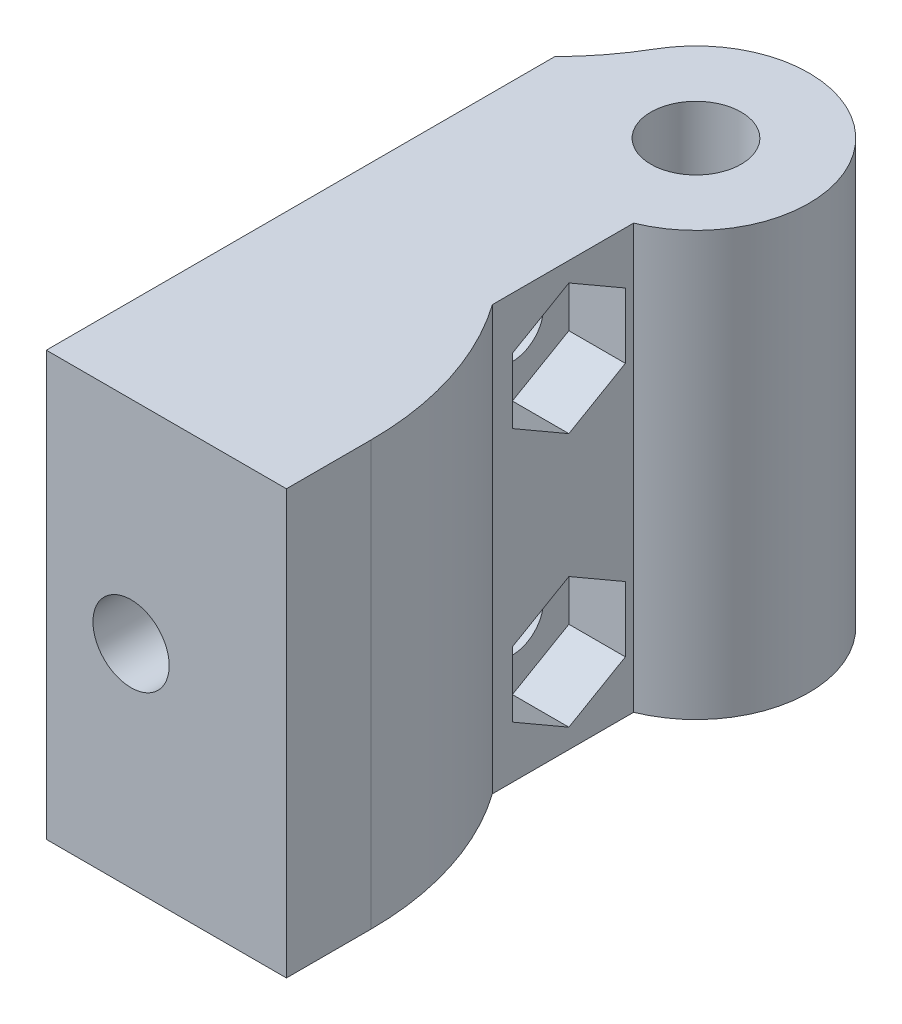
SolidWorks part; units mm, degrees
material "PLA"
ref_plane "前视基准面" through (0, 0, 0) normal (0, 0, 1) x (1, 0, 0)
ref_plane "上视基准面" through (0, 0, 0) normal (0, 1, 0) x (1, 0, 0)
ref_plane "右视基准面" through (0, 0, 0) normal (1, 0, 0) x (0, 0, -1)
sketch "草图1" plane through (0, 0, 0) normal (0, 1, 0) x (1, 0, 0)
  line L2 (-5, -18) -> (3.5, -18)
  line L3 (3.5, -18) -> (3.5, -15)
  line L5 (1.5, -3.7081) -> (1.5, -8.7081)
  line L7 (-5, -18) -> (-5, 0)
  line L8 (-4, 0) -> (-5, 0)
  circle A0 centre (0, 0) radius 1.6
  arc A1 (1.5, -3.7081) -> (-4, 0) centre (0, 0) ccw
  arc A2 (3.5, -15) -> (1.5, -8.7081) centre (-7.397, -15) ccw
  dimension "D1" = 3.2
  dimension "D2" = 4
  dimension "D3" = 18
  dimension "D4" = 8.5
  dimension "D5" = 3
  dimension "D6" = 5
  dimension "D7" = 5
  dimension "D8" = 6.5
extrude "凸台-拉伸1" add sketch "草图1" along normal mid plane 15
sketch "草图3" plane through (1.5, 0, 0) normal (1, 0, 0) x (0, 0, -1)
  line L0 (0, 0) -> (-18, 0) construction
  line L1 (-3.7081, 7.5) -> (-3.7081, -7.5) construction
  line L2 (-6, -7.5) -> (-6, 7.5) construction
  line L3 (-18, 7.5) -> (-18, -7.5) construction
  line L4 (-8.7081, 7.5) -> (-3.7081, 7.5) construction
  circle A0 centre (-6, 4.5) radius 1.1
  circle A1 centre (-6, -4.5) radius 1.1
  circle A2 centre (-6, 4.5) radius 2.2919 construction
  dimension "D1" = 2.2
  dimension "D4" = 4.5838
  dimension "D2" = 9
  dimension "D3" = 6
extrude "切除-拉伸1" cut sketch "草图3" against normal through all both and the other way through all
fillet "圆角1" radius 10 1 edges at (-4, 0, 0)
sketch "草图6" plane through (0, 0, 18) normal (0, 0, 1) x (1, 0, 0)
  line L0 (-2, 0) -> (0, 0) construction
  line L1 (-5, 7.5) -> (-5, -7.5) construction
  circle A0 centre (-2, 0) radius 1.35
  dimension "D2" = 2.7
  dimension "D1" = 3
extrude "切除-拉伸2" cut sketch "草图6" against normal blind 4
sketch "草图7" plane through (-5, 0, 0) normal (-1, 0, 0) x (0, 0, 1)
  line L0 (0, 0) -> (13, 0) construction
  line L1 (0, 7.5) -> (0, -7.5) construction
  line L2 (18, 7.5) -> (18, -7.5) construction
  line L3 (15, -2.5) -> (11, -2.5)
  line L4 (15, -2.5) -> (15, 2.5)
  line L5 (15, 2.5) -> (11, 2.5)
  line L6 (11, -2.5) -> (11, 2.5)
  line L7 (13, 2.5) -> (13, -2.5) construction
  line L8 (15, 0) -> (11, 0) construction
  dimension "D1" = 3
  dimension "D2" = 4
  dimension "D3" = 5
extrude "切除-拉伸3" cut sketch "草图7" against normal blind 6
sketch "草图8" plane through (1.5, 0, 0) normal (1, 0, 0) x (0, 0, -1)
  line L0 (0, 0) -> (-8.7081, 0) construction
  line L1 (-8, 5.6547) -> (-8, 3.3453)
  line L2 (-8, 3.3453) -> (-6, 2.1906)
  line L3 (-6, 2.1906) -> (-4, 3.3453)
  line L4 (-4, 3.3453) -> (-4, 5.6547)
  line L5 (-4, 5.6547) -> (-6, 6.8094)
  line L6 (-6, 6.8094) -> (-8, 5.6547)
  line L7 (-8.7081, 7.5) -> (-8.7081, -7.5) construction
  line L8 (-6, -6.8094) -> (-8, -5.6547)
  line L9 (-4, -5.6547) -> (-6, -6.8094)
  line L10 (-4, -3.3453) -> (-4, -5.6547)
  line L11 (-6, -2.1906) -> (-4, -3.3453)
  line L12 (-8, -3.3453) -> (-6, -2.1906)
  line L13 (-8, -5.6547) -> (-8, -3.3453)
  circle A0 centre (-6, 4.5) radius 2 construction
  dimension "D1" = 4
extrude "切除-拉伸4" cut sketch "草图8" against normal blind 2 and the other way through all
